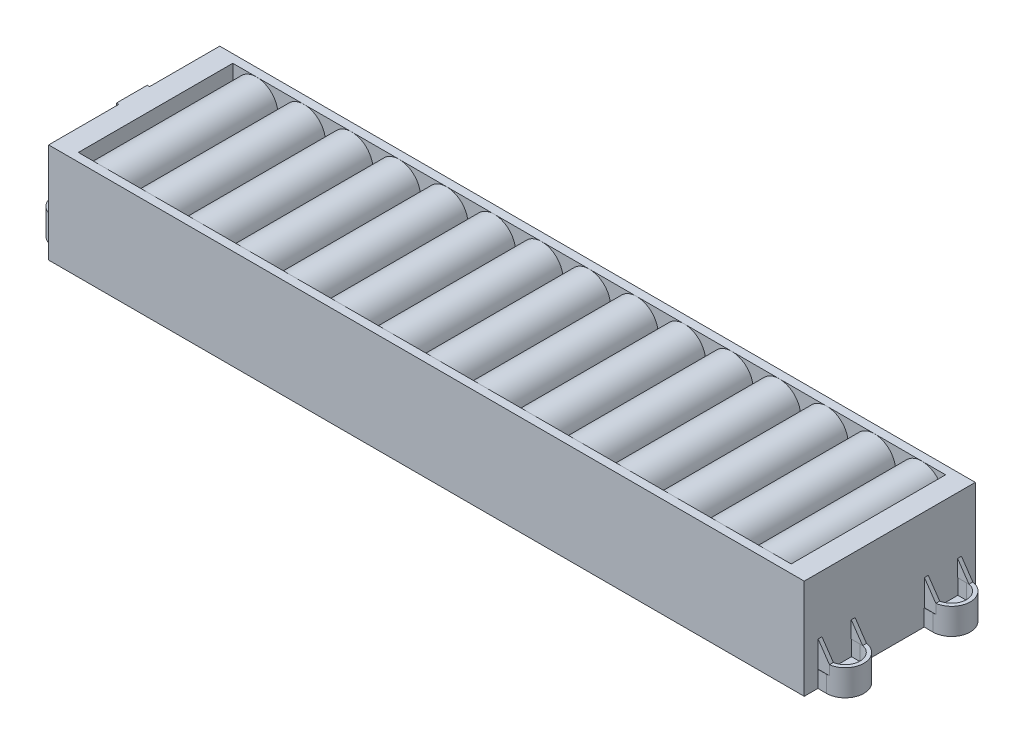
SolidWorks part; units mm, degrees
ref_plane "Front Plane" through (0, 0, 0) normal (0, 0, 1) x (1, 0, 0)
ref_plane "Top Plane" through (0, 0, 0) normal (0, 1, 0) x (1, 0, 0)
ref_plane "Right Plane" through (0, 0, 0) normal (1, 0, 0) x (0, 0, -1)
sketch "Sketch1" plane through (0, 0, 0) normal (0, 1, 0) x (1, 0, 0)
  line L1 (159, -36) -> (-159, -36)
  line L2 (159, -36) -> (159, 36)
  line L3 (159, 36) -> (-159, 36)
  line L4 (-159, -36) -> (-159, 36)
  line L5 (159, -36) -> (-159, 36) construction
  line L6 (159, 36) -> (-159, -36) construction
  point P0 (0, 0)
  dimension "D1" = 318
  dimension "D2" = 72
extrude "Boss-Extrude1" add sketch "Sketch1" along normal blind 42
sketch "Sketch2" plane through (0, 0, 0) normal (0, -1, 0) x (1, 0, 0)
  line L0 (162.625, 14.5) -> (159, 14.5)
  line L1 (159, 36) -> (159, -36) construction
  line L2 (162.625, 30.25) -> (159, 30.25)
  line L4 (162.625, 16.1) -> (159, 16.1)
  line L5 (162.625, 28.65) -> (159, 28.65)
  line L7 (159, 30.25) -> (159, 28.65)
  line L8 (159, 16.1) -> (159, 14.5)
  line L9 (162.625, -14.5) -> (159, -14.5)
  line L10 (159, -14.5) -> (159, -16.1)
  line L11 (159, -30.25) -> (162.625, -30.25)
  line L12 (159, -28.65) -> (162.625, -28.65)
  line L13 (162.625, -16.1) -> (159, -16.1)
  line L14 (159, -28.65) -> (159, -30.25)
  line L15 (-162.625, -14.5) -> (-159, -14.5)
  line L16 (-159, -36) -> (-159, 36) construction
  line L17 (-159, -14.5) -> (-159, -16.1)
  line L18 (-159, -30.25) -> (-162.625, -30.25)
  line L19 (-162.625, 14.5) -> (-159, 14.5)
  line L20 (-159, 14.5) -> (-159, 16.1)
  line L21 (-159, 30.25) -> (-162.625, 30.25)
  line L22 (-159, 28.65) -> (-162.625, 28.65)
  line L23 (-162.625, 16.1) -> (-159, 16.1)
  line L24 (-159, -28.65) -> (-162.625, -28.65)
  line L25 (-162.625, -16.1) -> (-159, -16.1)
  line L26 (-159, -28.65) -> (-159, -30.25)
  line L27 (-159, 28.65) -> (-159, 30.25)
  arc A0 (162.625, 14.5) -> (162.625, 30.25) centre (162.625, 22.375) ccw
  arc A1 (162.625, 16.1) -> (162.625, 28.65) centre (162.625, 22.375) ccw
  arc A2 (162.625, -30.25) -> (162.625, -14.5) centre (162.625, -22.375) ccw
  arc A3 (162.625, -28.65) -> (162.625, -16.1) centre (162.625, -22.375) ccw
  arc A4 (-162.625, 30.25) -> (-162.625, 14.5) centre (-162.625, 22.375) ccw
  arc A5 (-162.625, -14.5) -> (-162.625, -30.25) centre (-162.625, -22.375) ccw
  arc A6 (-162.625, 28.65) -> (-162.625, 16.1) centre (-162.625, 22.375) ccw
  arc A7 (-162.625, -16.1) -> (-162.625, -28.65) centre (-162.625, -22.375) ccw
  point P8 (159, 0)
  point P9 (170.5, 22.375)
  point P15 (170.5, -22.375)
  point P26 (-170.5, 22.375)
  point P28 (-170.5, -22.375)
  point P40 (-159, 0)
  dimension "D1" = 14.5
  dimension "D2" = 15.75
  dimension "D3" = 11.5
  dimension "D5" = 14.5
  dimension "D6" = 15.75
  dimension "D7" = 11.5
  dimension "D9" = 14.5
  dimension "D10" = 14.5
  dimension "D11" = 15.75
  dimension "D12" = 15.75
  dimension "D13" = 11.5
  dimension "D14" = 11.5
  dimension "D4" = 1.6
  dimension "D8" = 1.6
  dimension "D15" = 1.6
  dimension "D16" = 1.6
extrude "Boss-Extrude2" add sketch "Sketch2" against normal blind 11 separate body
sketch "Sketch3" plane through (0, 0, 0) normal (0, -1, 0) x (1, 0, 0)
  line L0 (159, 28.65) -> (159, 16.1)
  line L1 (159, 16.1) -> (162.625, 16.1)
  line L2 (162.625, 28.65) -> (159, 28.65)
  line L3 (161.825, 22.375) -> (165.075, 22.375) construction
  line L4 (161.825, 24.55) -> (165.075, 24.55)
  line L5 (161.825, 20.2) -> (165.075, 20.2)
  arc A0 (162.625, 28.65) -> (162.625, 16.1) centre (162.625, 22.375) cw
  arc A1 (161.825, 24.55) -> (161.825, 20.2) centre (161.825, 22.375) ccw
  arc A2 (165.075, 20.2) -> (165.075, 24.55) centre (165.075, 22.375) ccw
  arc A3 (162.625, 14.5) -> (162.625, 30.25) centre (162.625, 22.375) ccw construction
  point P13 (163.45, 22.375)
  point P18 (167.25, 22.375)
  point P19 (170.5, 22.375)
  dimension "D1" = 2.175
  dimension "D2" = 3.25
  dimension "D3" = 3.25
extrude "Boss-Extrude3" add sketch "Sketch3" against normal blind 4.5
mirror "Mirror5" about plane through (0, 0, 0) normal (1, 0, 0) of "Boss-Extrude3" second plane through (0, 0, 0) second plane normal (0, 0, 1)
sketch "Sketch4" plane through (0, 0, 0) normal (0, 0, 1) x (1, 0, 0)
  line L2 (-159, 42) -> (159, 42) construction
  line L3 (-159, 42) -> (-159, 0) construction
  line L10 (-131, 33) -> (-130, 33)
  line L11 (-130, 33) -> (-130, 42)
  line L12 (-159, 42) -> (159, 42) construction
  line L13 (-130, 42) -> (-150, 42)
  line L14 (-150, 42) -> (-150, 33)
  line L15 (-150, 33) -> (-149, 33)
  arc A0 (-131, 33) -> (-149, 33) centre (-140, 33) ccw
  point P2 (-140, 42)
  dimension "D1" = 18
  dimension "D2" = 19
  dimension "D3" = 1
  dimension "D4" = 1
extrude "Cut-Extrude1" cut sketch "Sketch4" against normal blind 32.5 and the other way blind 32.5 contours A0 L15 | A0 region at (-132.154, 39.1404, 0) region at (-147.846, 39.1404, 0)
pattern_linear "LPattern1" count 15 spacing 20 along (1, 0, 0) of "Cut-Extrude1"
ref_plane "Plane1" through (0, 21, 0) normal (0, -1, 0) x (-1, 0, 0)
mirror "Mirror7" about plane through (0, 21, 0) normal (0, -1, 0) of "LPattern1"
sketch "Sketch5" plane through (0, 0, 36) normal (0, 0, 1) x (1, 0, 0)
  line L0 (159, 11) -> (163.8, 11)
  line L1 (170.5, 11) -> (162.625, 11) construction
  line L2 (163.8, 11) -> (159, 18)
  line L3 (159, 42) -> (159, 0) construction
  line L4 (159, 18) -> (159, 11)
  dimension "D1" = 7
  dimension "D2" = 4.8
extrude "Boss-Extrude4" add sketch "Sketch5" against normal through all
sketch "Sketch6" plane through (0, 42, 0) normal (0, 1, 0) x (1, 0, 0)
  line L0 (159, -36) -> (159, 36) construction
  line L1 (159, -36) -> (163.8, -36)
  line L2 (159, -36) -> (159, -30.1618)
  line L3 (159, -30.1618) -> (163.8, -30.1618)
  line L4 (163.8, -36) -> (163.8, -30.1618)
  line L5 (163.8, -28.539) -> (159, -28.539)
  line L6 (163.8, -28.539) -> (163.8, -16.211)
  line L7 (163.8, -16.211) -> (159, -16.211)
  line L8 (159, -28.539) -> (159, -16.211)
  line L9 (163.8, -16.211) -> (163.8, -28.539) construction
  line L10 (159, 36) -> (159, -36) construction
  line L11 (163.8, -14.5882) -> (159, -14.5882)
  line L12 (163.8, -14.5882) -> (163.8, 14.5882)
  line L13 (163.8, 14.5882) -> (159, 14.5882)
  line L14 (159, -14.5882) -> (159, 14.5882)
  line L15 (163.8, 14.5882) -> (163.8, -14.5882) construction
  line L16 (163.8, 28.539) -> (163.8, 16.211) construction
  line L17 (163.8, 16.211) -> (159, 16.211)
  line L18 (163.8, 16.211) -> (163.8, 28.539)
  line L19 (163.8, 28.539) -> (159, 28.539)
  line L20 (159, 16.211) -> (159, 28.539)
  line L22 (159, 36) -> (163.8, 36)
  line L23 (159, 36) -> (159, 30.1618)
  line L24 (159, 30.1618) -> (163.8, 30.1618)
  line L25 (163.8, 36) -> (163.8, 30.1618)
  arc A0 (162.625, -28.65) -> (162.625, -16.1) centre (162.625, -22.375) ccw construction
  arc A1 (163.8, 14.5882) -> (163.8, 30.1618) centre (162.625, 22.375) ccw construction
  arc A2 (162.625, 16.1) -> (162.625, 28.65) centre (162.625, 22.375) ccw construction
extrude "Cut-Extrude2" cut sketch "Sketch6" against normal blind 35
sketch "Sketch7" plane through (-159, 0, 0) normal (-1, 0, 0) x (0, 0, 1)
  line L0 (-36, 42) -> (36, 42) construction
  line L1 (-6.5, 42) -> (6.5, 42)
  line L2 (-6.5, 42) -> (-6.5, 32)
  line L3 (-6.5, 32) -> (6.5, 32)
  line L4 (6.5, 42) -> (6.5, 32)
  point P6 (0, 42)
  point P7 (0, 42)
  dimension "D1" = 13
  dimension "D2" = 10
extrude "Boss-Extrude5" add sketch "Sketch7" along normal blind 1
sketch "Sketch8" plane through (0, 4.5, 0) normal (0, 1, 0) x (1, 0, 0)
  line L1 (-168.9, -22.375) -> (-159, -22.375) construction
  line L2 (-159, -28.65) -> (-159, -16.1) construction
  line L3 (-159, -6.5) -> (-159, -36) construction
  line L4 (-162.625, -28.65) -> (-159, -28.65) construction
  line L5 (-159, -16.1) -> (-162.625, -16.1) construction
  line L6 (-162.625, -28.65) -> (-159, -28.65)
  line L7 (-159, -16.1) -> (-162.625, -16.1)
  line L8 (-159, -28.65) -> (-159, -16.1)
  arc A1 (-162.625, -16.1) -> (-162.625, -28.65) centre (-162.625, -22.375) ccw construction
  circle A2 centre (-164, -22.375) radius 4.75
  arc A3 (-162.625, -16.1) -> (-162.625, -28.65) centre (-162.625, -22.375) ccw
  dimension "D1" = 5
  dimension "D2" = 9.5
extrude "Boss-Extrude6" add sketch "Sketch8" along normal up to surface (6.5 mm away) up to face at (-162.5813, 11, 22.375)
mirror "Mirror8" about plane through (0, 0, 0) normal (0, 0, 1) of "Boss-Extrude6"
equation "\"D1@Sketch2\"=29/2"
equation "\"D1@Sketch3\"=4.35/2"
equation "\"D2@Sketch3\"=7.6-2*\"D1@Sketch3\""
equation "\"D5@Sketch2\"=\"D1@Sketch2\""
equation "\"D6@Sketch2\"=\"D2@Sketch2\""
equation "\"D7@Sketch2\"=\"D3@Sketch2\""
equation "\"D9@Sketch2\"=\"D1@Sketch2\""
equation "\"D10@Sketch2\"=\"D1@Sketch2\""
equation "\"D11@Sketch2\"=\"D2@Sketch2\""
equation "\"D12@Sketch2\"=\"D2@Sketch2\""
equation "\"D13@Sketch2\"=\"D3@Sketch2\""
equation "\"D14@Sketch2\"=\"D3@Sketch2\""
